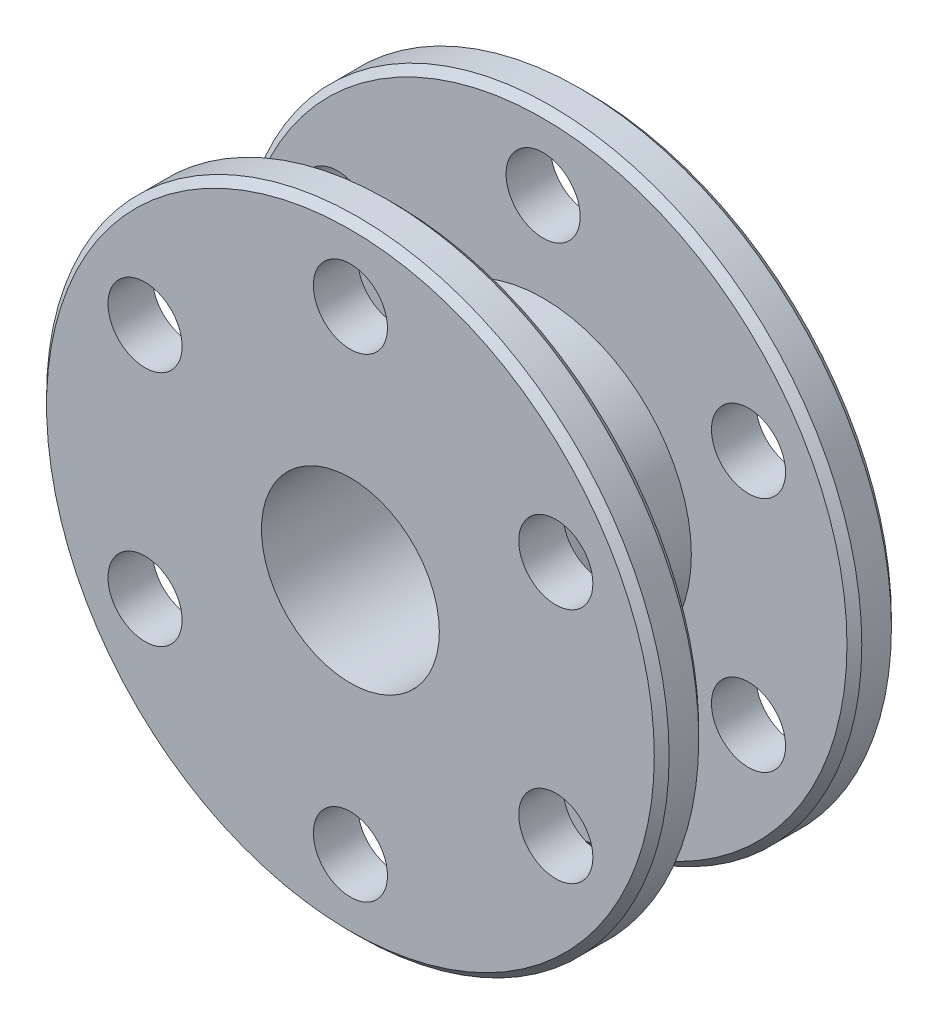
SolidWorks part; units mm, degrees
ref_plane "Front Plane" through (0, 0, 0) normal (0, 0, 1) x (1, 0, 0)
ref_plane "Top Plane" through (0, 0, 0) normal (0, 1, 0) x (1, 0, 0)
ref_plane "Right Plane" through (0, 0, 0) normal (1, 0, 0) x (0, 0, -1)
sketch "Sketch1" plane through (0, 0, 0) normal (0, 0, 1) x (1, 0, 0)
  line L0 (0, 23.7812) -> (0, -23.7812) construction
  line L1 (-12.5286, 0) -> (12.5286, 0) construction
  circle A0 centre (0, 0) radius 6
  circle A1 centre (0, 0) radius 10
  circle A2 centre (0, 0) radius 16 construction
  circle A3 centre (0, 0) radius 21
  circle A4 centre (0, 16) radius 2.5
  circle A5 centre (13.8564, 8) radius 2.5
  circle A6 centre (13.8564, -8) radius 2.5
  circle A7 centre (0, -16) radius 2.5
  circle A8 centre (-13.8564, -8) radius 2.5
  circle A9 centre (-13.8564, 8) radius 2.5
  point P4 (0, 0)
  point P8 (0, 0)
  point P27 (0, 0)
  dimension "D1" = 32
  dimension "D2" = 12
  dimension "D3" = 20
  dimension "D4" = 42
  dimension "D5" = 5
  dimension "D7" = 16
  dimension "D6" = 6
extrude "Boss-Extrude1" add sketch "Sketch1" along normal blind 16 contours A1 A0 region at (-9.7172, 0, 0)
extrude "Boss-Extrude2" add sketch "Sketch1<3>" along normal blind 3 contours A3 A9 A8 A7 A6 A5 A4 A1 region at (-20.406, 0, 0)
sketch "Sketch1<3>" plane through (0, 0, 0) normal (0, 0, 1) x (1, 0, 0) same geometry as "Sketch1"
ref_plane "Plane1" through (0, 0, 8) normal (0, 0, -1) x (-1, 0, 0)
mirror "Mirror1" about plane through (0, 0, 8) normal (0, 0, -1) of "Boss-Extrude2"
chamfer "Chamfer1" distance 0.5 angle 45 4 edges at (21, 0, 0) (21, 0, 3) (21, 0, 13) (21, 0, 16)
